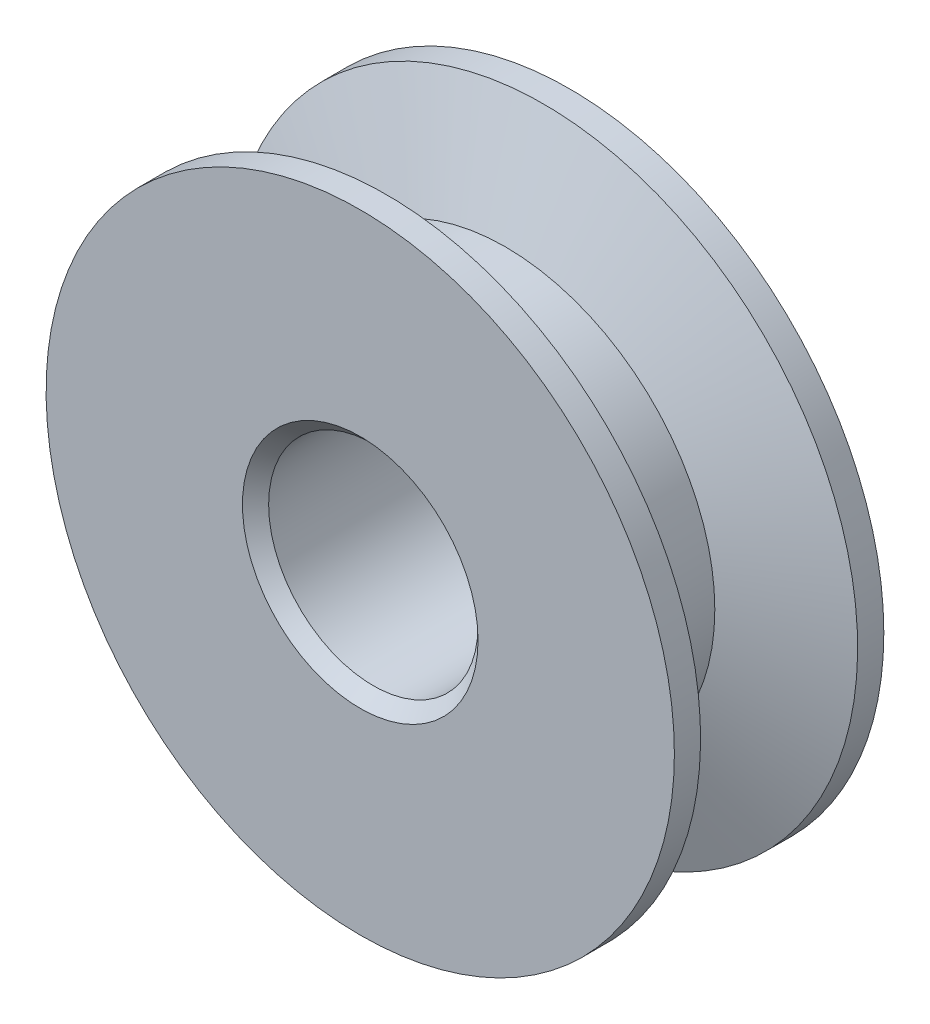
SolidWorks part; units mm, degrees
material "6061-T6 (SS)"
ref_plane "Front Plane" through (0, 0, 0) normal (0, 0, 1) x (1, 0, 0)
ref_plane "Top Plane" through (0, 0, 0) normal (0, 1, 0) x (1, 0, 0)
ref_plane "Right Plane" through (0, 0, 0) normal (1, 0, 0) x (0, 0, -1)
sketch "Sketch1" plane through (0, 0, 0) normal (0, 0, 1) x (1, 0, 0)
  circle A0 centre (0, 0) radius 19.05
  circle A1 centre (0, 0) radius 6.35
  dimension "D1" = 38.1
  dimension "D2" = 12.7
extrude "Extrude1" add sketch "Sketch1" along normal mid plane 12.7
sketch "Sketch2" plane through (0, 0, 0) normal (1, 0, 0) x (0, 0, -1)
  line L0 (-4.7625, 19.05) -> (4.7625, 19.05)
  line L2 (4.7625, 19.05) -> (2.4513, 12.7)
  line L3 (2.4513, 12.7) -> (-2.4513, 12.7)
  line L4 (-2.4513, 12.7) -> (-4.7625, 19.05)
  line L5 (-6.35, 0) -> (6.35, 0) construction
  line L6 (-6.35, 19.05) -> (-6.35, -19.05) construction
  line L7 (6.35, -19.05) -> (6.35, 19.05) construction
  point P2 (0, 19.05)
  point P5 (0, 12.7)
  dimension "D1" = 19.05
  dimension "D2" = 6.35
  dimension "D3" = 9.525
  dimension "D4" = 40
chamfer "Chamfer1" distance 0.7937 angle 45 2 edges at (6.35, 0, -6.35) (6.35, 0, 6.35)
revolve "Cut-Revolve1" cut sketch "Sketch2" angle 360 about L5
